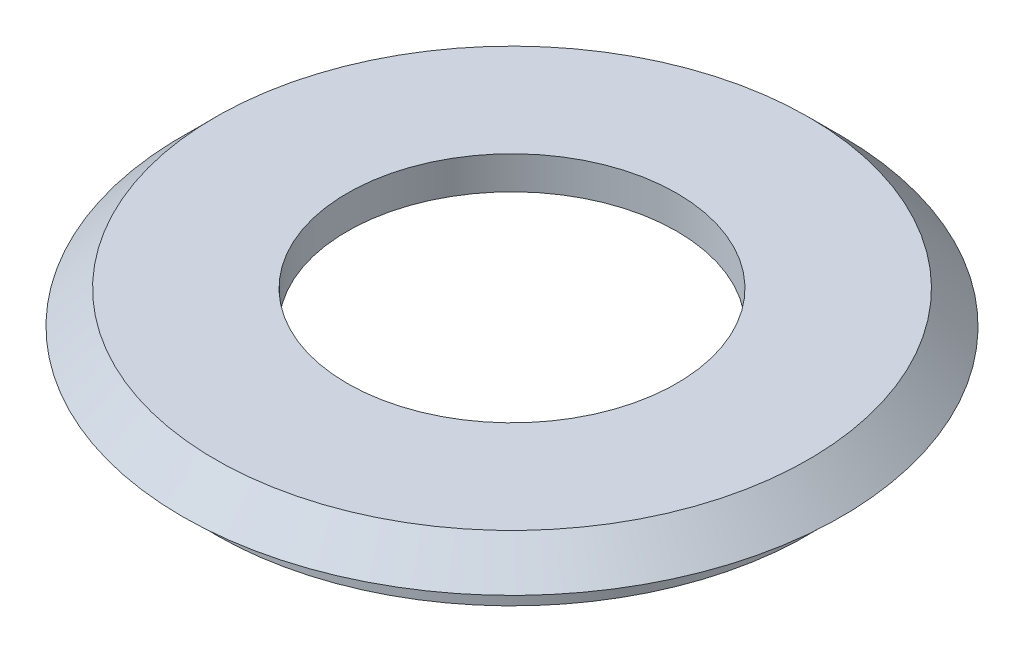
SolidWorks part; units mm, degrees
ref_plane "Front Plane" through (0, 0, 0) normal (0, 0, 1) x (1, 0, 0)
ref_plane "Top Plane" through (0, 0, 0) normal (0, 1, 0) x (1, 0, 0)
ref_plane "Right Plane" through (0, 0, 0) normal (1, 0, 0) x (0, 0, -1)
sketch "Sketch1" plane through (0, 0, 0) normal (0, 1, 0) x (1, 0, 0)
  circle A0 centre (0, 0) radius 100
  dimension "D1" = 200
extrude "Boss-Extrude1" add sketch "Sketch1" along normal blind 10
chamfer "Chamfer1" distance 10 angle 45 1 edges at (0, 10, 100)
sketch "Sketch2" plane through (0, 0, 0) normal (0, -1, 0) x (1, 0, 0)
  circle A0 centre (0, 0) radius 89.75
  circle A1 centre (0, 0) radius 85
  dimension "D1" = 179.5
  dimension "D2" = 170
extrude "Boss-Extrude2" add sketch "Sketch2" along normal blind 10
sketch "Sketch3" plane through (0, 10, 0) normal (0, 1, 0) x (1, 0, 0)
  circle A0 centre (0, 0) radius 50
  dimension "D1" = 100
extrude "Cut-Extrude1" cut sketch "Sketch3" against normal blind 20
